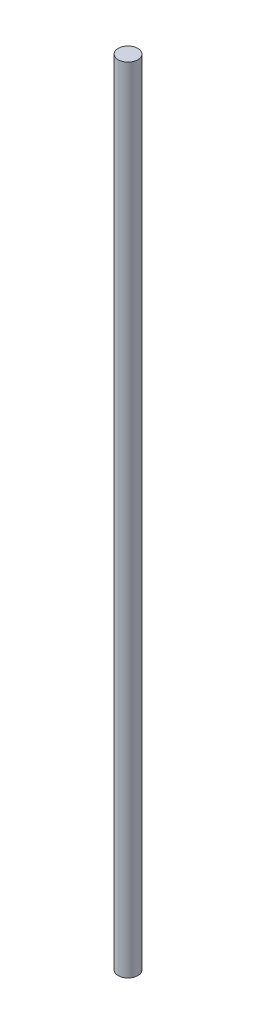
SolidWorks part; units mm, degrees
ref_plane "Front Plane" through (0, 0, 0) normal (0, 0, 1) x (1, 0, 0)
ref_plane "Top Plane" through (0, 0, 0) normal (0, 1, 0) x (1, 0, 0)
ref_plane "Right Plane" through (0, 0, 0) normal (1, 0, 0) x (0, 0, -1)
sketch "Sketch1" plane through (0, 0, 0) normal (0, 1, 0) x (1, 0, 0)
  circle A0 centre (0, 0) radius 5.08
  dimension "D1" = 10.16
extrude "Boss-Extrude1" add sketch "Sketch1" along normal blind 408.94
